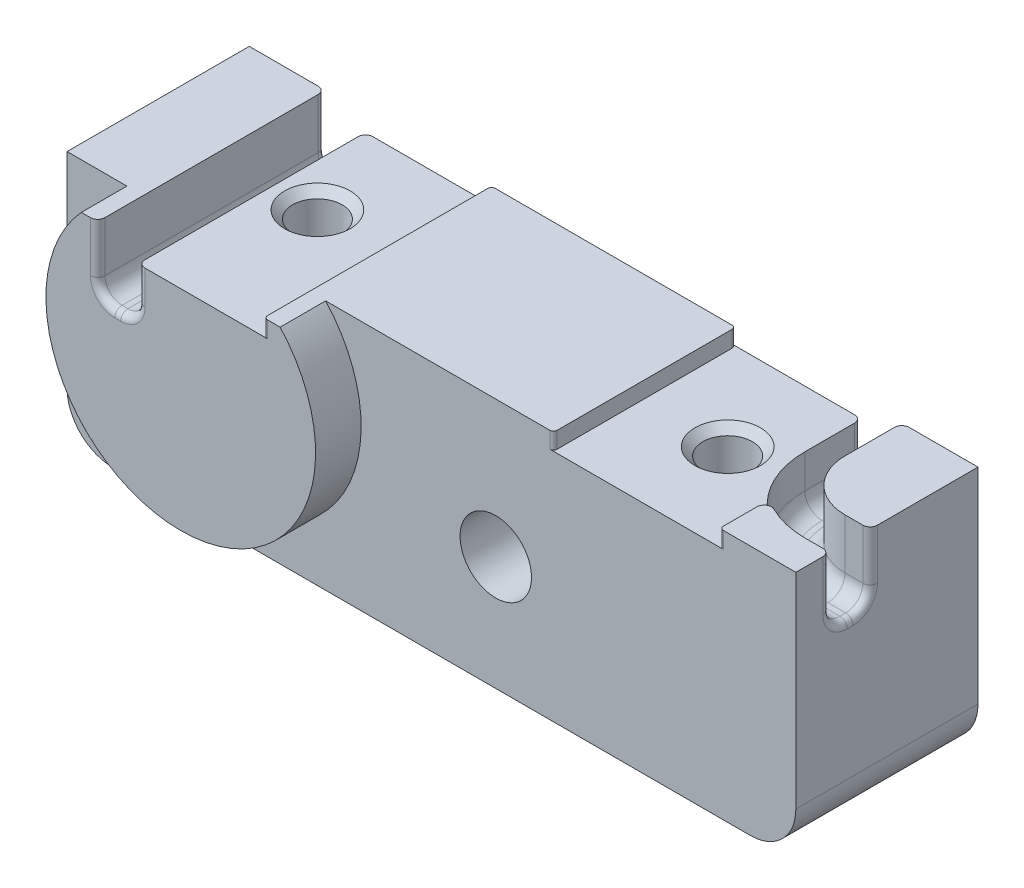
SolidWorks part; units mm, degrees
ref_plane "Front Plane" through (0, 0, 0) normal (0, 0, 1) x (1, 0, 0)
ref_plane "Top Plane" through (0, 0, 0) normal (0, 1, 0) x (1, 0, 0)
ref_plane "Right Plane" through (0, 0, 0) normal (1, 0, 0) x (0, 0, -1)
sketch "Sketch1" plane through (0, 0, 0) normal (0, 0, 1) x (1, 0, 0)
  line L2 (-25.4, 0) -> (-25.4, -17.4752)
  line L3 (-25.4, -17.4752) -> (25.4, -17.4752)
  line L4 (25.4, 0) -> (25.4, -17.4752)
  line L8 (25.4, 0) -> (-25.4, 0)
  circle A1 centre (-14.3002, -6.35) radius 8.89 construction
  point P0 (-14.3002, 0)
  point P3 (14.3002, 0)
  dimension "D4" = 14.3002
  dimension "D11" = 17.78
  dimension "D2" = 6.35
  dimension "D3" = 14.3002
  dimension "D10" = 50.8
  dimension "D13" = 17.4752
extrude "Boss-Extrude1" add sketch "Sketch1" against normal blind 12.7
ref_axis "Axis1" through (-14.3002, -6.35, 0) along (0, 0, 1)
sketch "Sketch2" plane through (0, 0, 0) normal (0, 0, 1) x (1, 0, 0)
  line L0 (-21.2284, 0) -> (-7.372, 0)
  line L1 (25.4, 0) -> (-25.4, 0) construction
  arc A0 (-21.2284, 0) -> (-7.372, 0) centre (-14.3002, -6.35) ccw
  dimension "D1" = 18.796
extrude "Boss-Extrude2" add sketch "Sketch2" along normal blind 3.175
sketch "Sketch12" plane through (0, 0, 0) normal (0, 1, 0) x (1, 0, 0)
  line L1 (8.509, 20.1976) -> (20.0914, 20.1976)
  line L2 (8.509, 20.1976) -> (8.509, -10.8488)
  line L3 (8.509, -10.8488) -> (20.0914, -10.8488)
  line L4 (20.0914, 20.1976) -> (20.0914, -10.8488)
  line L5 (-20.0914, 20.9017) -> (-8.509, 20.9017)
  line L6 (-20.0914, 20.9017) -> (-20.0914, -16.3186)
  line L7 (-20.0914, -16.3186) -> (-8.509, -16.3186)
  line L8 (-8.509, 20.9017) -> (-8.509, -16.3186)
  point P8 (14.3002, 20.1976)
  point P9 (-14.3002, 20.9017)
  dimension "D1" = 11.5824
  dimension "D2" = 11.5824
extrude "Cut-Extrude5" cut sketch "Sketch12" against normal blind 1.143
hole_wizard "#9 (0.196) Diameter Hole1" positions "Sketch4" profile "Sketch3" hole size "#9" standard "ANSI Inch" end condition through all
sketch "Sketch4" plane through (33.7312, -2.2084, 0) normal (0, 0, 1) x (1, 0, 0)
  point P0 (-29.2478, -7.3166)
  dimension "D1" = 9.525
  dimension "D2" = 4.4834
  dimension "D3" = 19.05
  dimension "D4" = 3.175
sketch "Sketch3" plane through (4.4834, -9.525, 0) normal (1, 0, 0) x (0, -1, 0)
  line L0 (0, 0) -> (0, 12.7)
  line L1 (0, 12.7) -> (2.4892, 12.7)
  line L2 (2.4892, 12.7) -> (2.4892, 0)
  line L5 (2.4892, 0) -> (0, 0)
  line L11 (0, -6.35) -> (0, 107.95) construction
  dimension "Thru Hole Dia." = 4.9784
  dimension "Thru Hole Depth" = 12.7
fillet "Fillet1" radius 3.175 2 edges at (-25.4, -17.4752, -6.35) (25.4, -17.4752, -6.35)
hole_wizard "#8-32 Tapped Hole2" positions "Sketch9" profile "Sketch8" tap size "#8-32" standard "Ansi Inch" end condition through all
sketch "Sketch9" plane through (26.7, -1.143, -0.7583) normal (0, 1, 0) x (-1, 0, 0)
  point P0 (12.3998, -5.5917)
  point P8 (41.0002, -5.5917)
  dimension "D1" = 6.35
cosmetic thread "Hole Thread4" parameters "D2"=4.1656
cosmetic thread "Hole Thread5" parameters "D2"=4.1656
sketch "Sketch8" plane through (14.3002, -1.143, -6.35) normal (1, 0, 0) x (0, 0, 1)
  line L0 (0, 0) -> (0, 16.3322)
  line L1 (0, 16.3322) -> (1.7272, 16.3322)
  line L2 (1.7272, 16.3322) -> (1.7272, 0.5588)
  line L3 (1.7272, 0.5588) -> (2.286, 0)
  line L5 (2.286, 0) -> (0, 0)
  line L6 (-1.7272, 0.5588) -> (-2.286, 0) construction
  line L11 (0, -6.35) -> (0, 107.95) construction
  dimension "Thru Tap Drill Dia." = 3.4544
  dimension "Thru Tap Drill Depth" = 16.3322
  dimension "Near C'Sink Dia." = 4.572
  dimension "Near C'Sink Angle" = 90
sketch "Sketch11" plane through (0, 0, 0) normal (0, 1, 0) x (1, 0, 0)
  line L0 (20.0914, 20.2981) -> (20.0914, 8.7376)
  line L1 (23.6474, 5.1816) -> (32.1109, 5.1816)
  line L2 (17.2974, 20.2981) -> (17.2974, 8.7376)
  line L3 (-20.0914, 16.8401) -> (-17.2974, 16.8401)
  line L4 (17.2974, 20.2981) -> (20.0914, 20.2981)
  line L5 (-20.0914, -6.3579) -> (-20.0914, 16.8401)
  line L6 (32.1109, 5.1816) -> (32.1109, 2.3876)
  line L7 (32.1109, 2.3876) -> (23.6474, 2.3876)
  line L10 (-17.2974, 16.8401) -> (-17.2974, -6.3579)
  line L11 (-17.2974, -6.3579) -> (-20.0914, -6.3579)
  line L12 (20.0914, 0) -> (20.0914, 12.7) construction
  line L13 (-20.0914, 12.7) -> (-20.0914, -3.175) construction
  arc A0 (20.0914, 8.7376) -> (23.6474, 5.1816) centre (23.6474, 8.7376) ccw
  arc A1 (23.6474, 2.3876) -> (17.2974, 8.7376) centre (23.6474, 8.7376) cw
  dimension "D2" = 3.556
  dimension "D4" = 2.3876
  dimension "D1" = 2.794
  dimension "D3" = 2.794
extrude "Cut-Extrude4" cut sketch "Sketch11" against normal offset from surface (4.699 mm away) 3.556 up to face at (14.3002, -1.143, -4.064)
fillet "Fillet2" radius 1.1938 8 edges at (20.0914, -4.699, -10.7188) (17.2974, -4.699, -10.7188) (-20.0914, -4.699, -4.7625) (-17.2974, -4.699, -4.7625) (24.5237, -4.699, -2.3876) (19.1573, -4.699, -4.2475) (24.5237, -4.699, -5.1816) (21.1329, -4.699, -6.2231)
fillet "Fillet3" radius 0.508 1 edges at (20.0914, -0.5715, -3.4767)
fillet "Fillet4" radius 0.254 5 edges at (-8.509, -0.5715, 3.175) (-8.509, -0.5715, -12.7) (8.509, -0.5715, -12.7) (8.509, -0.5715, 0) (20.0914, -0.5715, 0)
sketch "Sketch13" plane through (0, -1.143, 0) normal (0, 1, 0) x (1, 0, 0)
  line L0 (20.0914, 0.254) -> (20.0914, 2.5942) construction
  line L1 (20.0914, 8.7376) -> (20.0914, 12.7) construction
  line L2 (20.0914, 0.254) -> (20.0914, 8.7376)
  line L3 (20.0914, 8.7376) -> (20.0914, 12.7)
  arc A0 (20.0914, 0.254) -> (20.3454, 0) centre (20.3454, 0.254) ccw construction
  arc A1 (20.0914, 0.254) -> (20.3454, 0) centre (20.3454, 0.254) ccw
sketch "Sketch14" plane through (0, 0, 0) normal (0, 1, 0) x (1, 0, 0)
  line L0 (-25.4, 12.7) -> (-25.4, 0) construction
  line L1 (25.4, 12.7) -> (25.4, 5.1816) construction
  line L2 (-25.4, 12.446) -> (-25.4, 0)
  line L3 (25.4, 12.446) -> (25.4, 0)
  line L4 (25.146, 12.7) -> (-25.146, 12.7)
  arc A0 (25.146, 12.7) -> (25.4, 12.446) centre (25.146, 12.446) cw
  arc A1 (-25.146, 12.7) -> (-25.4, 12.446) centre (-25.146, 12.446) ccw
  dimension "D1" = 0.254
sketch "Sketch15" plane through (0, 0, 3.175) normal (0, 0, 1) x (1, 0, 0)
  line L0 (-25.4, -8.255) -> (25.4, -8.255)
  line L1 (-25.4, 0) -> (-25.4, -14.3002) construction
  line L2 (25.4, -14.3002) -> (25.4, 0) construction
  dimension "D1" = 8.255
sketch "Sketch16" plane through (0, 0, -12.7) normal (0, 0, -1) x (-1, 0, 0)
  circle A0 centre (-4.4834, -9.525) radius 4.1656
  dimension "D1" = 8.3312
extrude "Cut-Extrude6" cut sketch "Sketch16" against normal blind 6.35
chamfer "Chamfer1" distance 0.254 angle 45 2 edges at (0.3178, -9.525, -12.7) (1.9942, -9.525, -6.35)
fillet "Fillet8" radius 0.508 20 edges at (-17.2974, -2.3241, 3.175) (-17.6471, -4.3493, 3.175) (-18.6944, -4.699, 3.175) (-19.7417, -4.3493, 3.175) (-20.0914, -1.7526, 3.175) (25.4, -1.7526, -5.1816) (25.4, -4.3493, -4.8319) (25.4, -4.699, -3.7846) (25.4, -4.3493, -2.7373) (20.0914, -1.7526, -12.7) (19.7417, -4.3493, -12.7) (18.6944, -4.699, -12.7) (17.6471, -4.3493, -12.7) (-17.2974, -2.3241, -12.7) (-17.6471, -4.3493, -12.7) (-18.6944, -4.699, -12.7) (-19.7417, -4.3493, -12.7) (25.4, -1.7526, -2.3876) (17.2974, -2.3241, -12.7) (-20.0914, -1.7526, -12.7)
